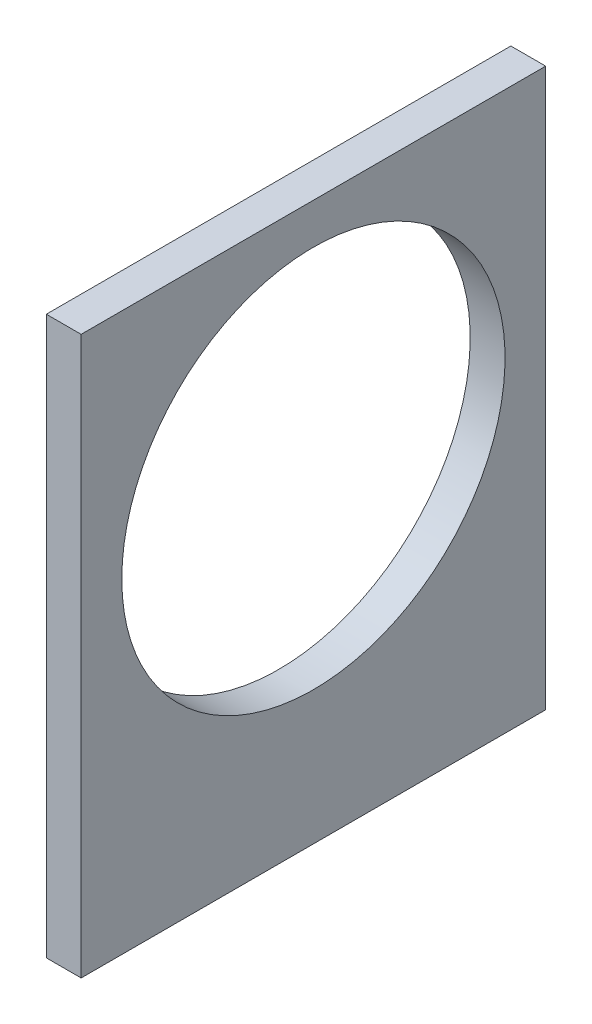
SolidWorks part; units mm, degrees
material "6061-T6 (SS)"
ref_plane "Front Plane" through (0, 0, 0) normal (0, 0, 1) x (1, 0, 0)
ref_plane "Top Plane" through (0, 0, 0) normal (0, 1, 0) x (1, 0, 0)
ref_plane "Right Plane" through (0, 0, 0) normal (1, 0, 0) x (0, 0, -1)
sketch "Sketch4" plane through (0, 0, 0) normal (1, 0, 0) x (0, 0, -1)
  line L1 (31.75, 38.1) -> (-31.75, 38.1)
  line L2 (31.75, 38.1) -> (31.75, -38.1)
  line L3 (31.75, -38.1) -> (-31.75, -38.1)
  line L4 (-31.75, 38.1) -> (-31.75, -38.1)
  line L5 (31.75, 38.1) -> (-31.75, -38.1) construction
  line L6 (31.75, -38.1) -> (-31.75, 38.1) construction
  circle A0 centre (0, 6.35) radius 26.1938
  point P0 (0, 0)
  dimension "D3" = 52.3875
  dimension "D1" = 31.75
  dimension "D2" = 63.5
  dimension "D4" = 76.2
extrude "Boss-Extrude2" add sketch "Sketch4" along normal blind 4.7625
sketch "Sketch5" plane through (0, 0, -31.75) normal (0, 0, -1) x (-1, 0, 0)
  line L0 (-4.7625, 38.1) -> (0, 38.1) construction
  line L1 (0, 38.1) -> (-2.3813, 38.1)
  line L2 (0, 38.1) -> (0, -23.1)
  line L3 (0, -23.1) -> (-2.3812, -23.1)
  line L4 (-2.3813, 38.1) -> (-2.3812, -23.1)
  dimension "D1" = 15
extrude "Cut-Extrude1" [suppressed] cut sketch "Sketch5" against normal through all
hole_wizard "Tap Drill for #6-32 Tap1" positions "Sketch6" profile "Sketch7" hole size "#6-32" standard "ANSI Inch"
sketch "Sketch6" plane through (0, -38.1, 0) normal (0, -1, 0) x (-1, 0, 0)
  line L4 (-4.7625, 31.75) -> (0, 31.75) construction
  line L6 (-4.7625, -31.75) -> (0, -31.75) construction
  point P0 (-2.3813, 29.3687)
  point P2 (-2.3813, -29.3687)
  point P29 (-2.3813, 31.75)
  dimension "D2" = 2.3813
  dimension "D3" = 2.3813
sketch "Sketch7" plane through (2.3813, -38.1, -29.3687) normal (1, 0, 0) x (0, 0, -1)
  line L0 (0, 0) -> (0, 13.5127)
  line L1 (0, 13.5127) -> (1.3525, 12.7)
  line L2 (1.3525, 12.7) -> (1.3525, 0)
  line L5 (1.3525, 0) -> (0, 0)
  line L10 (0, 13.5127) -> (-1.3526, 12.7) construction
  line L11 (0, -6.35) -> (0, 107.95) construction
  dimension "Hole Dia." = 2.7051
  dimension "Hole Depth" = 12.7
  dimension "Drill Angle" = 118
